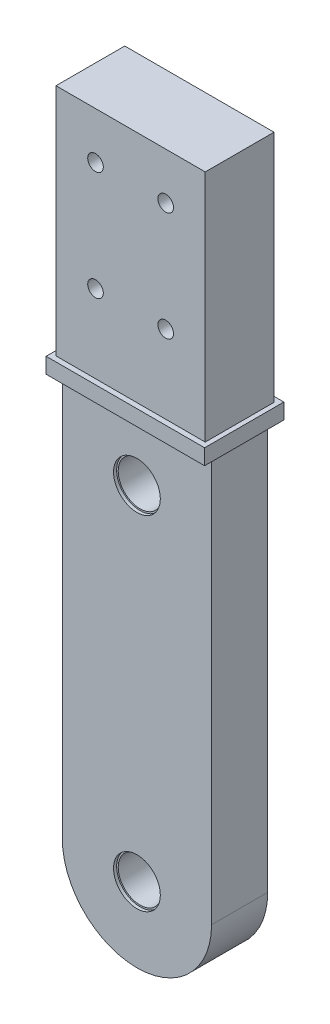
SolidWorks part; units mm, degrees
ref_plane "Front Plane" through (0, 0, 0) normal (0, 0, 1) x (1, 0, 0)
ref_plane "Top Plane" through (0, 0, 0) normal (0, 1, 0) x (1, 0, 0)
ref_plane "Right Plane" through (0, 0, 0) normal (1, 0, 0) x (0, 0, -1)
sketch "Sketch1" plane through (0, 0, 0) normal (0, 0, 1) x (1, 0, 0)
  line L0 (-23.925, 0) -> (-23.925, 100)
  line L1 (-23.925, 100) -> (23.925, 100)
  line L2 (23.925, 100) -> (23.925, 0)
  line L3 (-23.925, 0) -> (-23.925, -110)
  line L4 (-11.25, 85) -> (11.25, 85) construction
  line L5 (-11.25, 85) -> (-11.25, 50) construction
  line L6 (-11.25, 50) -> (11.25, 50) construction
  line L7 (11.25, 85) -> (11.25, 50) construction
  line L8 (0, 0) -> (0, -110) construction
  line L10 (23.925, 0) -> (23.925, -110)
  circle A0 centre (0, 0) radius 7
  circle A2 centre (-11.25, 85) radius 2.5
  circle A3 centre (11.25, 85) radius 2.5
  circle A4 centre (11.25, 50) radius 2.5
  circle A5 centre (-11.25, 50) radius 2.5
  circle A6 centre (0, -110) radius 7
  arc A7 (23.925, -110) -> (0, -133.925) centre (0, -110) cw
  arc A8 (-23.925, -110) -> (0, -133.925) centre (0, -110) ccw
  point P13 (0, 50)
  point P23 (0, 0)
  point P24 (0, 0)
  point P25 (0, 100)
  point P26 (0, 0)
  dimension "D1" = 14
  dimension "D4" = 5
  dimension "D9" = 14
  dimension "D11" = 23.925
  dimension "D2" = 47.85
  dimension "D3" = 100
  dimension "D5" = 35
  dimension "D6" = 15
  dimension "D7" = 22.5
  dimension "D8" = 110
extrude "Boss-Extrude1" add sketch "Sketch1" along normal mid plane 18 from surface starting at plane "Front Plane"
sketch "Sketch3" plane through (0, 0, 0) normal (0, 0, 1) x (1, 0, 0)
  line L0 (23.925, 100) -> (23.925, -110) construction
  line L1 (-23.925, 100) -> (23.925, 100)
  line L2 (-23.925, 100) -> (-23.925, 35)
  line L3 (-23.925, 35) -> (23.925, 35)
  line L4 (23.925, 100) -> (23.925, 35)
  line L5 (-11.25, 85) -> (-11.25, 100) construction
  line L6 (-11.25, 50) -> (-11.25, 35) construction
  circle A0 centre (-11.25, 50) radius 2.5
  circle A1 centre (11.25, 50) radius 2.5
  circle A2 centre (11.25, 85) radius 2.5
  circle A3 centre (-11.25, 85) radius 2.5
  circle A4 centre (-11.25, 85) radius 2.5 construction
extrude "Boss-Extrude2" add sketch "Sketch3" along normal mid plane 22.05
sketch "Sketch4" plane through (0, 0, 9) normal (0, 0, 1) x (1, 0, 0)
  circle A0 centre (0, -110) radius 7.5
  dimension "D1" = 15
extrude "Cut-Extrude1" cut sketch "Sketch4" against normal blind 1
sketch "Sketch5" plane through (0, 0, -9) normal (0, 0, -1) x (-1, 0, 0)
  circle A0 centre (0, -110) radius 7.5
  dimension "D1" = 15
extrude "Cut-Extrude2" cut sketch "Sketch5" against normal blind 1
sketch "Sketch6" plane through (0, 0, 9) normal (0, 0, 1) x (1, 0, 0)
  circle A0 centre (0, 0) radius 7.5
  dimension "D1" = 15
extrude "Cut-Extrude3" cut sketch "Sketch6" against normal blind 1
sketch "Sketch7" plane through (0, 0, -9) normal (0, 0, -1) x (-1, 0, 0)
  circle A0 centre (0, 0) radius 7.5
  dimension "D1" = 15
extrude "Cut-Extrude4" cut sketch "Sketch7" against normal blind 1
sketch "Sketch8" plane through (0, 35, 0) normal (0, -1, 0) x (1, 0, 0)
  line L1 (-25.4, -12.7) -> (25.4, -12.7)
  line L2 (-25.4, -12.7) -> (-25.4, 12.7)
  line L3 (-25.4, 12.7) -> (25.4, 12.7)
  line L4 (25.4, -12.7) -> (25.4, 12.7)
  line L5 (-25.4, -12.7) -> (25.4, 12.7) construction
  line L6 (-25.4, 12.7) -> (25.4, -12.7) construction
  point P0 (0, 0)
  dimension "D1" = 50.8
  dimension "D2" = 25.4
extrude "Boss-Extrude3" add sketch "Sketch8" along normal blind 5 from offset 10
sketch "Sketch9" plane through (0, 35, 0) normal (0, -1, 0) x (1, 0, 0)
  line L1 (-23.925, -11.025) -> (23.925, -11.025)
  line L2 (-23.925, -11.025) -> (-23.925, 11.025)
  line L3 (-23.925, 11.025) -> (23.925, 11.025)
  line L4 (23.925, -11.025) -> (23.925, 11.025)
  line L5 (-23.925, -11.025) -> (23.925, 11.025) construction
  line L6 (-23.925, 11.025) -> (23.925, -11.025) construction
  point P0 (0, 0)
extrude "Boss-Extrude4" add sketch "Sketch9" along normal up to surface (10 mm away) up to face at (0, 25, 0)
equation "\"tube_length\"= 1.5ft"
